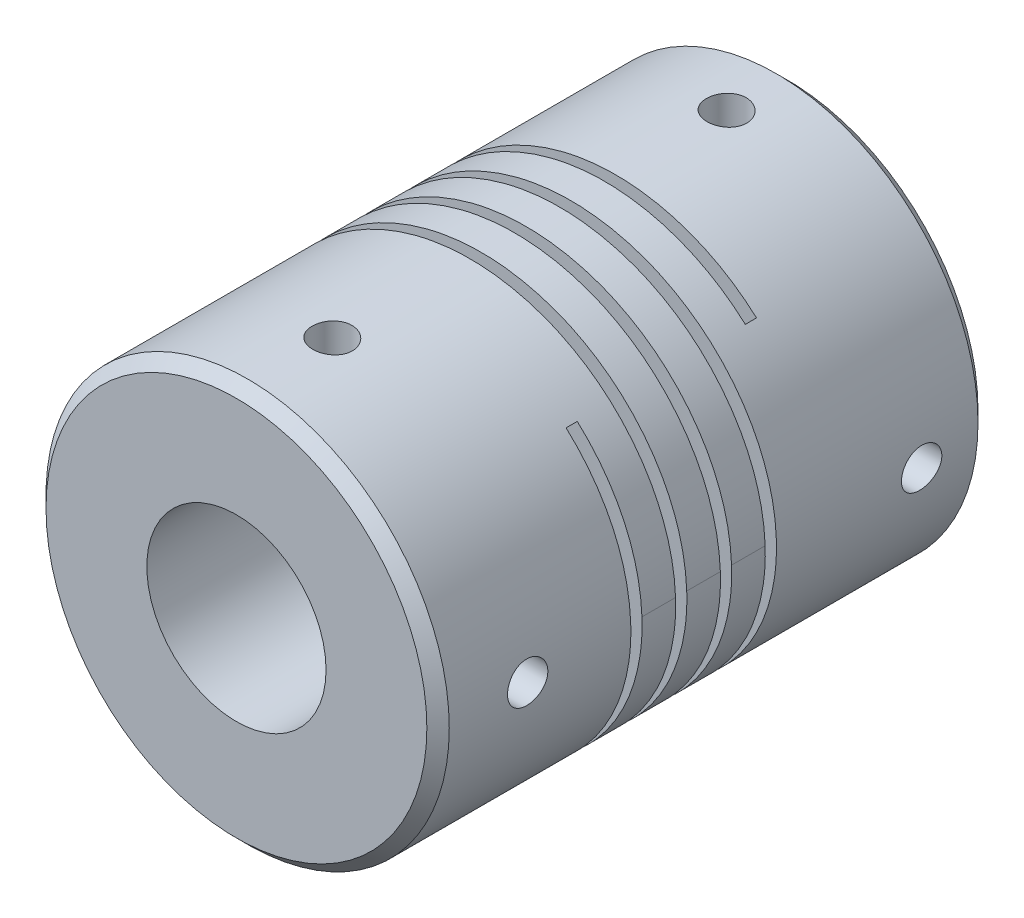
SolidWorks part; units mm, degrees
material "Alumina"
ref_plane "Front Plane" through (0, 0, 0) normal (0, 0, 1) x (1, 0, 0)
ref_plane "Top Plane" through (0, 0, 0) normal (0, 1, 0) x (1, 0, 0)
ref_plane "Right Plane" through (0, 0, 0) normal (1, 0, 0) x (0, 0, -1)
sketch "Sketch1" plane through (0, 0, 0) normal (0, 0, 1) x (1, 0, 0)
  circle A0 centre (0, 0) radius 4
  circle A1 centre (0, 0) radius 9
  dimension "D1" = 18
  dimension "D2" = 8
extrude "Boss-Extrude1" add sketch "Sketch1" along normal blind 24.6 contours A1 A0
sketch "Sketch2" plane through (0, 0, 24.6) normal (0, 0, 1) x (1, 0, 0)
  circle A0 centre (0, 0) radius 4
  dimension "D1" = 8
ref_plane "Plane1" through (0, 0, 11) normal (0, 0, -1) x (-1, 0, 0)
sketch "Sketch3" plane through (0, 0, 11) normal (0, 0, -1) x (-1, 0, 0)
  circle A0 centre (0, 0) radius 9
  dimension "D1" = 18
curve "Helix/Spiral1" pitch 2 height 8 turns 4
sketch "Sketch5" plane through (0, 0, 0) normal (1, 0, 0) x (0, 0, -1)
  line L1 (-8, 10) -> (-8.5, 10)
  line L2 (-8, 10) -> (-8, -2)
  line L3 (-8, -2) -> (-8.5, -2)
  line L4 (-8.5, 10) -> (-8.5, -2)
  dimension "D1" = 0.5
  dimension "D2" = 12
  dimension "D3" = 10
  dimension "D4" = 8
sweep "Cut-Sweep2" cut profiles "Sketch5" path "Helix/Spiral1"
ref_plane "Plane2" through (0, 9, 0) normal (0, 1, 0) x (1, 0, 0)
sketch "Sketch6" plane through (0, 9, 0) normal (0, 1, 0) x (1, 0, 0)
  circle A0 centre (0.2778, -20.6) radius 0.9
  circle A1 centre (0.2778, -3) radius 0.9
  dimension "D1" = 1.8
extrude "Cut-Extrude2" cut sketch "Sketch6" against normal up to next
ref_plane "Plane3" through (9, 0, 0) normal (1, 0, 0) x (0, 0, -1)
sketch "Sketch7" plane through (9, 0, 0) normal (1, 0, 0) x (0, 0, -1)
  circle A0 centre (-20.6, 0) radius 0.9
  circle A1 centre (-3, -0.5173) radius 0.9
  dimension "D1" = 1.8
extrude "Cut-Extrude3" cut sketch "Sketch7" against normal up to next
chamfer "Chanfrein1" distance 0.5 angle 45 2 edges at (9, 0, 0) (9, 0, 24.6)
